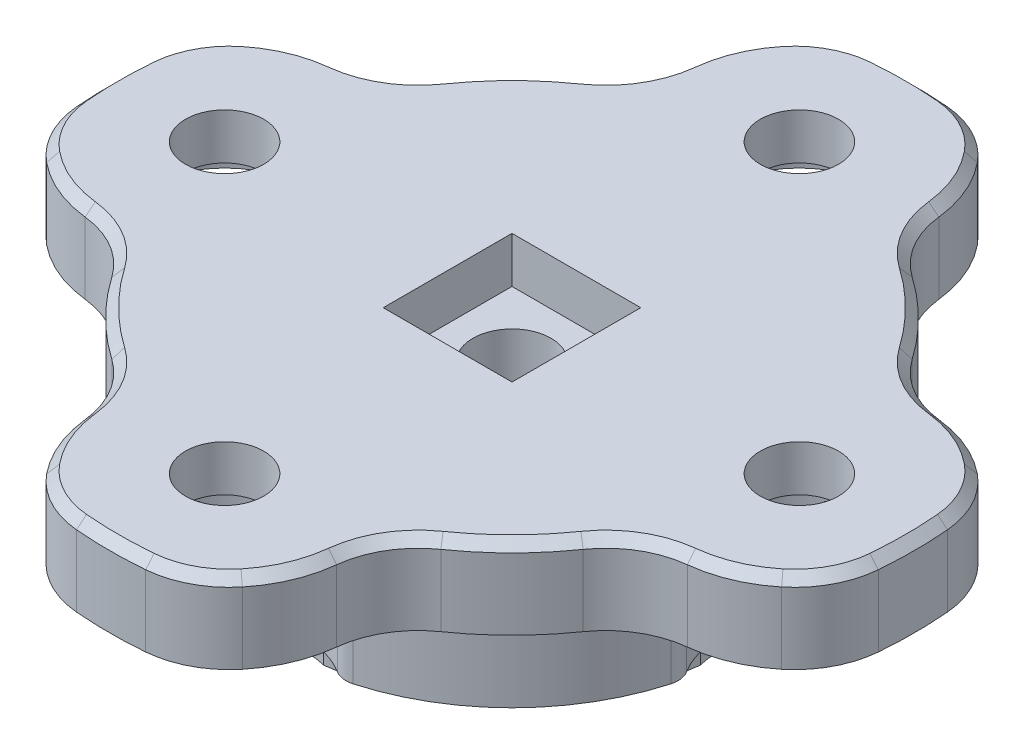
SolidWorks part; units mm, degrees
material "ABS"
ref_plane "Plan de face" through (0, 0, 0) normal (0, 0, 1) x (1, 0, 0)
ref_plane "Plan de dessus" through (0, 0, 0) normal (0, 1, 0) x (1, 0, 0)
ref_plane "Plan de droite" through (0, 0, 0) normal (1, 0, 0) x (0, 0, -1)
sketch "Esquisse1" plane through (0, 0, 0) normal (0, 1, 0) x (1, 0, 0)
  circle A0 centre (0, 0) radius 10
  dimension "D1" = 20
extrude "Boss.-Extru.1" add sketch "Esquisse1" along normal blind 4
sketch "Esquisse8" plane through (0, 4, 0) normal (0, 1, 0) x (1, 0, 0)
  circle A2 centre (0, 0) radius 11
  circle A3 centre (0, 0) radius 11
  dimension "D1" = 1
extrude "Boss.-Extru.4" add sketch "Esquisse8" along normal blind 0.5
sketch "Esquisse3" plane through (0, 4.5, 0) normal (0, 1, 0) x (1, 0, 0)
  circle A0 centre (0, 0) radius 17.5
  circle A1 centre (-12.5, 0) radius 1.7
  circle A2 centre (0, 12.5) radius 1.7
  circle A3 centre (12.5, 0) radius 1.7
  circle A4 centre (0, -12.5) radius 1.7
  point P14 (0, 0)
  dimension "D1" = 35
  dimension "D3" = 3.4
  dimension "D4" = 4
  dimension "D2" = 12.5
extrude "Boss.-Extru.2" add sketch "Esquisse3" along normal blind 3.5
sketch "Esquisse4" plane through (0, 4.5, 0) normal (0, -1, 0) x (1, 0, 0)
  circle A0 centre (0, -12.5) radius 3.55
  circle A1 centre (-12.5, 0) radius 3.55
  circle A2 centre (0, 12.5) radius 3.55
  circle A3 centre (12.5, 0) radius 3.55
  circle A4 centre (12.5, 0) radius 1.7 construction
  point P12 (0, 0)
  dimension "D1" = 7.1
  dimension "D2" = 4
extrude "Enlèv. mat.-Extru.2" cut sketch "Esquisse4" against normal blind 1.5 and the other way through all
sketch "Esquisse11" plane through (0, 8, 0) normal (0, 1, 0) x (1, 0, 0)
  arc A0 (-5.3652, -11.29) -> (5.3652, -11.29) centre (0, -12.5) ccw
  arc A1 (-11.29, 5.3652) -> (-11.29, -5.3652) centre (-12.5, 0) ccw
  arc A2 (5.3652, 11.29) -> (-5.3652, 11.29) centre (0, 12.5) ccw
  arc A3 (11.29, -5.3652) -> (11.29, 5.3652) centre (12.5, 0) ccw
  arc A4 (5.3652, -11.29) -> (11.29, -5.3652) centre (0, 0) ccw
  arc A5 (11.29, 5.3652) -> (5.3652, 11.29) centre (0, 0) ccw
  arc A6 (-5.3652, 11.29) -> (-11.29, 5.3652) centre (0, 0) ccw
  arc A7 (-11.29, -5.3652) -> (-5.3652, -11.29) centre (0, 0) ccw
  circle A8 centre (12.5, 0) radius 3.55 construction
  point P12 (0, 0)
  dimension "D2" = 5.5
  dimension "D1" = 4
extrude "Enlèv. mat.-Extru.3" cut sketch "Esquisse11" against normal through all flip side to cut
fillet "Congé1" radius 4 16 edges at (-11.29, 6.25, -5.3652) (-5.3652, 6.25, -11.29) (5.3652, 6.25, -11.29) (11.29, 6.25, -5.3652) (11.29, 6.25, 5.3652) (5.3652, 6.25, 11.29) (-11.29, 6.25, 5.3652) (-5.3652, 6.25, 11.29) (-17.29, 6.25, -2.7029) (-17.29, 6.25, 2.7029) (-2.7029, 6.25, -17.29) (2.7029, 6.25, -17.29) (17.29, 6.25, -2.7029) (17.29, 6.25, 2.7029) (-2.7029, 6.25, 17.29) (2.7029, 6.25, 17.29)
fillet "Congé2" radius 1 8 edges at (2.24, 2, 9.7459) (-2.24, 2, 9.7459) (-9.7459, 2, 2.24) (-9.7459, 2, -2.24) (-2.24, 2, -9.7459) (2.24, 2, -9.7459) (9.7459, 2, 2.24) (9.7459, 2, -2.24)
chamfer "Chanfrein2" distance 0.4 angle 45 32 edges at (3.0275, 8, -16.9877) (0, 8, -17.5) (5.0717, 8, -14.6278) (-3.0275, 8, -16.9877) (6.003, 8, -11.4906) (-5.0717, 8, -14.6278) (8.8388, 8, -8.8388) (-6.003, 8, -11.4906) (11.4906, 8, -6.003) (-8.8388, 8, -8.8388) (14.6278, 8, -5.0717) (-11.4906, 8, -6.003) (16.9877, 8, -3.0275) (-14.6278, 8, -5.0717) (17.5, 8, 0) (-16.9877, 8, -3.0275) (16.9877, 8, 3.0275) (-17.5, 8, 0) (14.6278, 8, 5.0717) (-16.9877, 8, 3.0275) (11.4906, 8, 6.003) (-14.6278, 8, 5.0717) (8.8388, 8, 8.8388) (-11.4906, 8, 6.003) (6.003, 8, 11.4906) (-8.8388, 8, 8.8388) (5.0717, 8, 14.6278) (-6.003, 8, 11.4906) (3.0275, 8, 16.9877) (-5.0717, 8, 14.6278) (0, 8, 17.5) (-3.0275, 8, 16.9877)
sketch "Esquisse12" plane through (0, 0, 0) normal (0, -1, 0) x (1, 0, 0)
  circle A0 centre (0, 0) radius 1.7
  dimension "D1" = 3.4
extrude "Enlèv. mat.-Extru.4" cut sketch "Esquisse12" against normal through all
sketch "Esquisse13" plane through (0, 8, 0) normal (0, 1, 0) x (1, 0, 0)
  line L1 (-2.8, -2.8) -> (2.8, -2.8)
  line L2 (-2.8, -2.8) -> (-2.8, 2.8)
  line L3 (-2.8, 2.8) -> (2.8, 2.8)
  line L4 (2.8, -2.8) -> (2.8, 2.8)
  line L5 (-2.8, -2.8) -> (2.8, 2.8) construction
  line L6 (-2.8, 2.8) -> (2.8, -2.8) construction
  point P0 (0, 0)
  dimension "D1" = 5.6
extrude "Enlèv. mat.-Extru.5" cut sketch "Esquisse13" against normal blind 2
sketch "Esquisse14" plane through (0, 0, 0) normal (0, -1, 0) x (1, 0, 0)
  circle A0 centre (0, 0) radius 9.1
  circle A1 centre (0, 0) radius 1.7 construction
  circle A2 centre (0, 0) radius 1.7
  dimension "D1" = 18.2
extrude "Boss.-Extru.5" add sketch "Esquisse14" along normal blind 0.5
sketch "Esquisse15" plane through (0, -0.5, 0) normal (0, -1, 0) x (1, 0, 0)
  circle A1 centre (12.5, 0) radius 3.55
  circle A2 centre (12.5, 0) radius 3.55
  circle A3 centre (0, 12.5) radius 3.55
  circle A4 centre (0, 12.5) radius 3.55
  circle A5 centre (-12.5, 0) radius 3.55
  circle A6 centre (-12.5, 0) radius 3.55
  circle A7 centre (0, -12.5) radius 3.55
  circle A8 centre (0, -12.5) radius 3.55
  dimension "D1" = 0
  dimension "D2" = 0
  dimension "D3" = 0
  dimension "D4" = 0
extrude "Enlèv. mat.-Extru.6" cut sketch "Esquisse15" against normal blind 0.5
